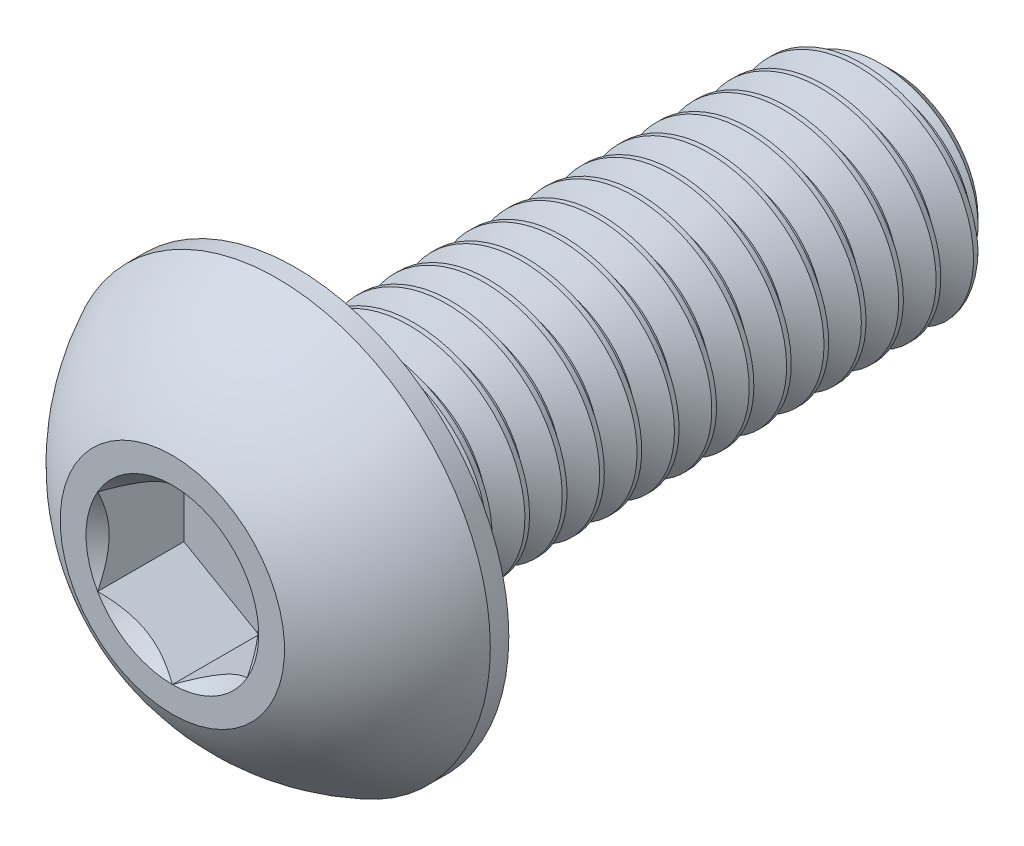
SolidWorks part; units mm, degrees
ref_plane "Front" through (0, 0, 0) normal (0, 0, 1) x (1, 0, 0)
ref_plane "Top" through (0, 0, 0) normal (0, 1, 0) x (1, 0, 0)
ref_plane "Right" through (0, 0, 0) normal (1, 0, 0) x (0, 0, -1)
sketch "Sketch1" plane through (0, 0, 0) normal (1, 0, 0) x (0, 0, -1)
  line L2 (1.65, 1.5) -> (9.65, 1.5)
  line L3 (9.65, 1.5) -> (9.65, 0)
  line L4 (9.65, 0) -> (1.65, 0)
  line L6 (1.4025, 2.85) -> (1.65, 2.85) construction
  line L7 (9.65, 1.5) -> (9.65, -1.5) construction
  line L8 (0, 0) -> (1.65, 0) construction
  line L9 (1.65, 2.85) -> (1.65, -2.85) construction
  line L11 (1.65, 1.5) -> (1.65, 0)
  line L13 (0, 1) -> (0, -1) construction
  line L14 (0, 1) -> (0, 1.5) construction
  line L15 (9.65, -1.5) -> (9.15, -1.5) construction
  arc A3 (0, 1.5) -> (1.4025, 2.85) centre (2.7948, 0) cw construction
  dimension "D1" = 0.2475
  dimension "Pitch" = 0.5
revolve "Revolve1" add sketch "Sketch1" angle 360 mid plane about L4
sketch "Sketch7" plane through (0, 0, 0) normal (1, 0, 0) x (0, 0, -1)
  line L6 (1.4025, 2.85) -> (1.65, 2.85) construction
  line L8 (0, 0) -> (1.65, 0) construction
  line L11 (1.65, 2.85) -> (1.65, -2.85) construction
  line L12 (1.4025, 2.85) -> (1.65, 2.85)
  line L13 (0, 0) -> (1.65, 0)
  line L14 (0, 1) -> (0, -1) construction
  line L15 (1.65, 2.85) -> (1.65, 0)
  line L16 (0, 1.5) -> (0, 0)
  arc A2 (1.4025, 2.85) -> (0, 1.5) centre (2.7948, 0) ccw construction
  arc A3 (1.4025, 2.85) -> (0, 1.5) centre (2.7948, 0) ccw
revolve "Revolve2" add sketch "Sketch7" angle 360 mid plane about L13
sketch "Sketch5" plane through (0, 0, 0) normal (0, 0, 1) x (1, 0, 0)
  line L1 (1, -0.5774) -> (1, 0.5774)
  line L2 (1, 0.5774) -> (0, 1.1547)
  line L3 (0, 1.1547) -> (-1, 0.5774)
  line L4 (-1, 0.5774) -> (-1, -0.5774)
  line L5 (-1, -0.5774) -> (0, -1.1547)
  line L6 (0, -1.1547) -> (1, -0.5774)
  circle A0 centre (0, 0) radius 1 construction
extrude "Cut-Extrude2" cut sketch "Sketch5" against normal blind 1.155
sketch "Sketch6" plane through (0, 0, 0) normal (0, 0, 1) x (1, 0, 0)
  circle A0 centre (0, 0) radius 1.1547
extrude "Cut-Extrude3" cut sketch "Sketch6" against normal blind 1.155 draft 45
sketch "Sketch11" plane through (0, 0, 0) normal (1, 0, 0) x (0, 0, -1)
  line L0 (1.65, -2.85) -> (1.65, 2.85)
  point P4 (1.65, 0)
split "Split1" trim tools "Sketch11" bodies to split 113 resulting bodies 119 120
sketch "Sketch10" plane through (0, 0, 0) normal (1, 0, 0) x (0, 0, -1)
  line L0 (9.65, 1.5) -> (9.65, -1.5) construction
  point P0 (8.9, -1.5)
  dimension "D1" = 0.75
sketch "Sketch3" plane through (0, 0, -9.65) normal (0, 0, -1) x (-1, 0, 0)
  circle A0 centre (0, 0) radius 1.5
curve "Helix/Spiral1" pitch 0.5 height 8.5 radius 1.5 centre (0, 0, -9.65) axis (0, 0, 1) start towards (0, 1, 0)
sketch "Sketch2" plane through (0, 0, 0) normal (1, 0, 0) x (0, 0, -1)
  line L0 (9.6187, 1.5541) -> (10.1187, 1.5541) construction
  line L1 (10.1187, 1.5541) -> (9.8687, 1.1211) construction
  line L2 (9.8687, 1.1211) -> (9.6187, 1.5541) construction
  line L3 (9.8687, 1.5541) -> (9.8687, 1.5) construction
  line L4 (9.8687, 1.5) -> (9.8687, 1.1752) construction
  line L5 (9.8687, 1.1752) -> (9.8687, 1.1211) construction
  line L6 (9.8375, 1.1752) -> (9.9, 1.1752)
  line L7 (9.65, 1.5) -> (10.0875, 1.5) construction
  line L8 (9.6344, 1.5271) -> (10.1031, 1.5271)
  line L9 (9.6344, 1.5271) -> (9.8375, 1.1752)
  line L10 (10.1031, 1.5271) -> (9.9, 1.1752)
  point P10 (9.8687, 1.1752)
  point P13 (9.8687, 1.5)
  point P16 (9.8687, 1.5271)
  dimension "D1" = 0.5
  dimension "D2" = 0.0625
chamfer "Chamfer1" distance 0.375 angle 45 1 edges at (0, 1.5, -9.65)
sweep "Cut-Sweep1" cut profiles "Sketch2" path "Helix/Spiral1" align with end faces yes
combine bodies "Combine1" operation type add bodies to combine 120 114
equation "\"D3@Helix/Spiral1\" = \"Lg@Sketch1\" + \"D4@Helix/Spiral1\""
equation "\"D1@Chamfer1\" = \"D4@Helix/Spiral1\" * .75"
equation "\"D1@Cut-Extrude2\" = \"Head Ht@Sketch1\" * .7"
equation "\"D1@Sketch1\" = \"Head Ht@Sketch1\" * .15"
equation "\"D1@Sketch10\" = \"D4@Helix/Spiral1\" * 1.5"
equation "\"D1@Cut-Extrude3\" = \"D1@Cut-Extrude2\""
equation "\"D4@Helix/Spiral1\"=\"Pitch@Sketch1\""
equation "\"D1@Sketch2\"=\"Pitch@Sketch1\""
equation "\"D2@Sketch2\"=\"D1@Sketch2\"/8"
